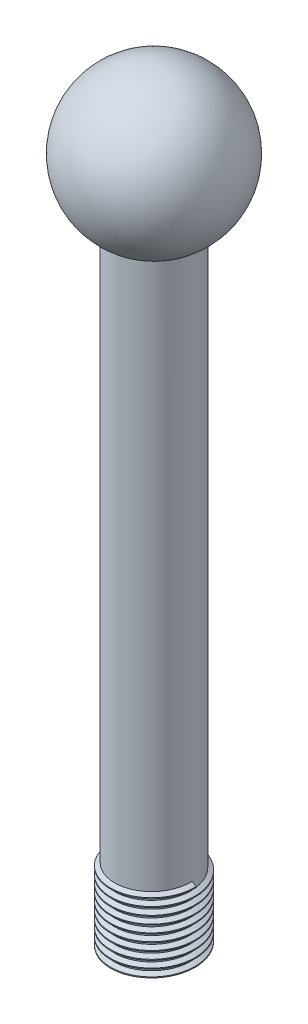
SolidWorks part; units mm, degrees
material "Cast Alloy Steel"
ref_plane "Front Plane" through (0, 0, 0) normal (0, 0, 1) x (1, 0, 0)
ref_plane "Top Plane" through (0, 0, 0) normal (0, 1, 0) x (1, 0, 0)
ref_plane "Right Plane" through (0, 0, 0) normal (1, 0, 0) x (0, 0, -1)
sketch "Sketch1" plane through (0, 0, 0) normal (0, 0, 1) x (1, 0, 0)
  line L0 (0, -50) -> (0, 50) construction
  line L1 (0, -50) -> (5, -50)
  line L2 (5, 31.3397) -> (5, -50)
  line L3 (0, 50) -> (0, -50)
  arc A0 (5, 31.3397) -> (0, 50) centre (0, 40) ccw
  arc A1 (0, 30) -> (5, 31.3397) centre (0, 40) ccw construction
  arc A2 (0, 50) -> (0, 30) centre (0, 40) ccw construction
  point P4 (0, 0)
  point P10 (0, 0)
  dimension "D2" = 20
  dimension "D1" = 90
  dimension "D3" = 10
revolve "Revolve1" add sketch "Sketch1" angle 360 about L0
thread "Thread1" pitch 1 method extrude trim with start face yes profile "Thread Profile1" start angle 0, offset 1, length 10, pitch 1, diameter 10
ref_plane "Plane1" through (5, -51, 0) normal (0, 0, 1) x (1, 0, 0)
sketch "Thread Profile1" plane through (5, -51, 0) normal (0, 0, 1) x (1, 0, 0)
  line L0 (0, 0) -> (0, 1) construction
  line L1 (0, 0) -> (0.5413, 0.3125)
  line L2 (0.5413, 0.3125) -> (0.5413, 0.4375)
  line L3 (0.5413, 0.4375) -> (0, 0.75)
  line L4 (0.5413, 0.375) -> (0, 0.375) construction
  line L11 (0, 0) -> (0, 0.75)
  point P2 (0, 0)
  dimension "Pitch" = 1
  dimension "Profile_Angle" = 60
  dimension "Profile_Land" = 0.125
  dimension "Profile_Height" = 0.5413
